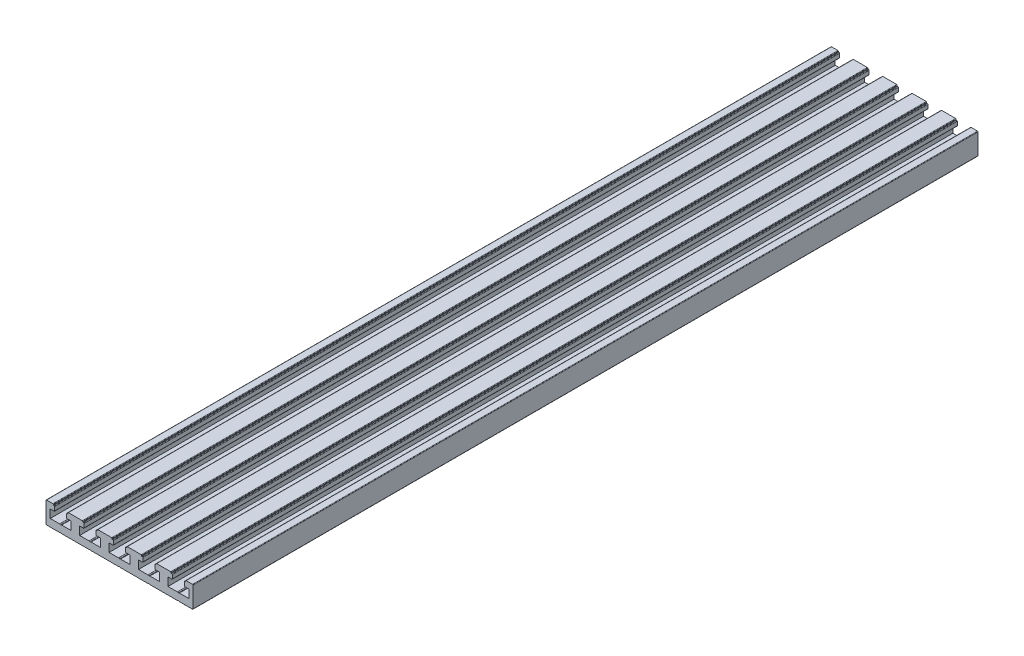
SolidWorks part; units mm, degrees
material "6061-T6 (SS)"
ref_plane "Front Plane" through (0, 0, 0) normal (0, 0, 1) x (1, 0, 0)
ref_plane "Top Plane" through (0, 0, 0) normal (0, 1, 0) x (1, 0, 0)
ref_plane "Right Plane" through (0, 0, 0) normal (1, 0, 0) x (0, 0, -1)
sketch "Sketch1" plane through (0, 0, 0) normal (0, 0, -1) x (-1, 0, 0)
  line L0 (0, 1.72) -> (0, -1.72) construction
  line L1 (-37.45, 8.85) -> (-37.45, -1.65)
  line L2 (-37.2, -1.9) -> (-30.5436, -1.9)
  line L3 (-30.4589, -1.8852) -> (-30, -1.72)
  line L4 (-30, -1.72) -> (-29.5411, -1.8852)
  line L5 (-29.4564, -1.9) -> (-15.5436, -1.9)
  line L6 (-15.4589, -1.8852) -> (-15, -1.72)
  line L7 (-15, -1.72) -> (-14.5411, -1.8852)
  line L8 (-14.4564, -1.9) -> (-0.5436, -1.9)
  line L9 (-0.4589, -1.8852) -> (0, -1.72)
  line L10 (0, -1.72) -> (0.4589, -1.8852)
  line L11 (0.5436, -1.9) -> (14.4564, -1.9)
  line L12 (14.5411, -1.8852) -> (15, -1.72)
  line L13 (15, -1.72) -> (15.4589, -1.8852)
  line L14 (15.5436, -1.9) -> (29.4564, -1.9)
  line L15 (29.5411, -1.8852) -> (30, -1.72)
  line L16 (30, -1.72) -> (30.4589, -1.8852)
  line L17 (30.5436, -1.9) -> (37.2, -1.9)
  line L18 (37.45, -1.65) -> (37.45, 8.85)
  line L19 (37.2, 9.1) -> (33.95, 9.1)
  line L20 (33.7, 8.85) -> (33.7, 8.5)
  line L21 (33.7, 8.5) -> (33.32, 8.5)
  line L22 (33.07, 8.25) -> (33.07, 6.35)
  line L23 (33.32, 6.1) -> (35.3, 6.1)
  line L24 (35.3, 6.1) -> (35.3, 1.9)
  line L25 (35.3, 1.9) -> (30.5436, 1.9)
  line L26 (30.4589, 1.8852) -> (30, 1.72)
  line L27 (30, 1.72) -> (29.5411, 1.8852)
  line L28 (29.4564, 1.9) -> (24.7, 1.9)
  line L29 (24.7, 1.9) -> (24.7, 6.1)
  line L30 (24.7, 6.1) -> (26.68, 6.1)
  line L31 (26.93, 6.35) -> (26.93, 8.25)
  line L32 (26.68, 8.5) -> (26.3, 8.5)
  line L33 (26.3, 8.5) -> (26.3, 8.85)
  line L34 (26.05, 9.1) -> (18.95, 9.1)
  line L35 (18.7, 8.85) -> (18.7, 8.5)
  line L36 (18.7, 8.5) -> (18.32, 8.5)
  line L37 (18.07, 8.25) -> (18.07, 6.35)
  line L38 (18.32, 6.1) -> (20.3, 6.1)
  line L39 (20.3, 6.1) -> (20.3, 1.9)
  line L40 (20.3, 1.9) -> (15.5436, 1.9)
  line L41 (15.4589, 1.8852) -> (15, 1.72)
  line L42 (15, 1.72) -> (14.5411, 1.8852)
  line L43 (14.4564, 1.9) -> (9.7, 1.9)
  line L44 (9.7, 1.9) -> (9.7, 6.1)
  line L45 (9.7, 6.1) -> (11.68, 6.1)
  line L46 (11.93, 6.35) -> (11.93, 8.25)
  line L47 (11.68, 8.5) -> (11.3, 8.5)
  line L48 (11.3, 8.5) -> (11.3, 8.85)
  line L49 (11.05, 9.1) -> (3.95, 9.1)
  line L50 (3.7, 8.85) -> (3.7, 8.5)
  line L51 (3.7, 8.5) -> (3.32, 8.5)
  line L52 (3.07, 8.25) -> (3.07, 6.35)
  line L53 (3.32, 6.1) -> (5.3, 6.1)
  line L54 (5.3, 6.1) -> (5.3, 1.9)
  line L55 (5.3, 1.9) -> (0.5436, 1.9)
  line L56 (0.4589, 1.8852) -> (0, 1.72)
  line L57 (0, 1.72) -> (-0.4589, 1.8852)
  line L58 (-0.5436, 1.9) -> (-5.3, 1.9)
  line L59 (-5.3, 1.9) -> (-5.3, 6.1)
  line L60 (-5.3, 6.1) -> (-3.32, 6.1)
  line L61 (-3.07, 6.35) -> (-3.07, 8.25)
  line L62 (-3.32, 8.5) -> (-3.7, 8.5)
  line L63 (-3.7, 8.5) -> (-3.7, 8.85)
  line L64 (-3.95, 9.1) -> (-11.05, 9.1)
  line L65 (-11.3, 8.85) -> (-11.3, 8.5)
  line L66 (-11.3, 8.5) -> (-11.68, 8.5)
  line L67 (-11.93, 8.25) -> (-11.93, 6.35)
  line L68 (-11.68, 6.1) -> (-9.7, 6.1)
  line L69 (-9.7, 6.1) -> (-9.7, 1.9)
  line L70 (-9.7, 1.9) -> (-14.4564, 1.9)
  line L71 (-14.5411, 1.8852) -> (-15, 1.72)
  line L72 (-15, 1.72) -> (-15.4589, 1.8852)
  line L73 (-15.5436, 1.9) -> (-20.3, 1.9)
  line L74 (-20.3, 1.9) -> (-20.3, 6.1)
  line L75 (-20.3, 6.1) -> (-18.32, 6.1)
  line L76 (-18.07, 6.35) -> (-18.07, 8.25)
  line L77 (-18.32, 8.5) -> (-18.7, 8.5)
  line L78 (-18.7, 8.5) -> (-18.7, 8.85)
  line L79 (-18.95, 9.1) -> (-26.05, 9.1)
  line L80 (-26.3, 8.85) -> (-26.3, 8.5)
  line L81 (-26.3, 8.5) -> (-26.68, 8.5)
  line L82 (-26.93, 8.25) -> (-26.93, 6.35)
  line L83 (-26.68, 6.1) -> (-24.7, 6.1)
  line L84 (-24.7, 6.1) -> (-24.7, 1.9)
  line L85 (-24.7, 1.9) -> (-29.4564, 1.9)
  line L86 (-29.5411, 1.8852) -> (-30, 1.72)
  line L87 (-30, 1.72) -> (-30.4589, 1.8852)
  line L88 (-30.5436, 1.9) -> (-35.3, 1.9)
  line L89 (-35.3, 1.9) -> (-35.3, 6.1)
  line L90 (-35.3, 6.1) -> (-33.32, 6.1)
  line L91 (-33.07, 6.35) -> (-33.07, 8.25)
  line L92 (-33.32, 8.5) -> (-33.7, 8.5)
  line L93 (-33.7, 8.5) -> (-33.7, 8.85)
  line L94 (-33.95, 9.1) -> (-37.2, 9.1)
  arc A0 (-37.45, -1.65) -> (-37.2, -1.9) centre (-37.2, -1.65) ccw
  arc A1 (-30.5436, -1.9) -> (-30.4589, -1.8852) centre (-30.5436, -1.65) ccw
  arc A2 (-29.5411, -1.8852) -> (-29.4564, -1.9) centre (-29.4564, -1.65) ccw
  arc A3 (-15.5436, -1.9) -> (-15.4589, -1.8852) centre (-15.5436, -1.65) ccw
  arc A4 (-14.5411, -1.8852) -> (-14.4564, -1.9) centre (-14.4564, -1.65) ccw
  arc A5 (-0.5436, -1.9) -> (-0.4589, -1.8852) centre (-0.5436, -1.65) ccw
  arc A6 (0.4589, -1.8852) -> (0.5436, -1.9) centre (0.5436, -1.65) ccw
  arc A7 (14.4564, -1.9) -> (14.5411, -1.8852) centre (14.4564, -1.65) ccw
  arc A8 (15.4589, -1.8852) -> (15.5436, -1.9) centre (15.5436, -1.65) ccw
  arc A9 (29.4564, -1.9) -> (29.5411, -1.8852) centre (29.4564, -1.65) ccw
  arc A10 (30.4589, -1.8852) -> (30.5436, -1.9) centre (30.5436, -1.65) ccw
  arc A11 (37.2, -1.9) -> (37.45, -1.65) centre (37.2, -1.65) ccw
  arc A12 (37.45, 8.85) -> (37.2, 9.1) centre (37.2, 8.85) ccw
  arc A13 (33.95, 9.1) -> (33.7, 8.85) centre (33.95, 8.85) ccw
  arc A14 (33.32, 8.5) -> (33.07, 8.25) centre (33.32, 8.25) ccw
  arc A15 (33.07, 6.35) -> (33.32, 6.1) centre (33.32, 6.35) ccw
  arc A16 (30.5436, 1.9) -> (30.4589, 1.8852) centre (30.5436, 1.65) ccw
  arc A17 (29.5411, 1.8852) -> (29.4564, 1.9) centre (29.4564, 1.65) ccw
  arc A18 (26.68, 6.1) -> (26.93, 6.35) centre (26.68, 6.35) ccw
  arc A19 (26.93, 8.25) -> (26.68, 8.5) centre (26.68, 8.25) ccw
  arc A20 (26.3, 8.85) -> (26.05, 9.1) centre (26.05, 8.85) ccw
  arc A21 (18.95, 9.1) -> (18.7, 8.85) centre (18.95, 8.85) ccw
  arc A22 (18.32, 8.5) -> (18.07, 8.25) centre (18.32, 8.25) ccw
  arc A23 (18.07, 6.35) -> (18.32, 6.1) centre (18.32, 6.35) ccw
  arc A24 (15.5436, 1.9) -> (15.4589, 1.8852) centre (15.5436, 1.65) ccw
  arc A25 (14.5411, 1.8852) -> (14.4564, 1.9) centre (14.4564, 1.65) ccw
  arc A26 (11.68, 6.1) -> (11.93, 6.35) centre (11.68, 6.35) ccw
  arc A27 (11.93, 8.25) -> (11.68, 8.5) centre (11.68, 8.25) ccw
  arc A28 (11.3, 8.85) -> (11.05, 9.1) centre (11.05, 8.85) ccw
  arc A29 (3.95, 9.1) -> (3.7, 8.85) centre (3.95, 8.85) ccw
  arc A30 (3.32, 8.5) -> (3.07, 8.25) centre (3.32, 8.25) ccw
  arc A31 (3.07, 6.35) -> (3.32, 6.1) centre (3.32, 6.35) ccw
  arc A32 (0.5436, 1.9) -> (0.4589, 1.8852) centre (0.5436, 1.65) ccw
  arc A33 (-0.4589, 1.8852) -> (-0.5436, 1.9) centre (-0.5436, 1.65) ccw
  arc A34 (-3.32, 6.1) -> (-3.07, 6.35) centre (-3.32, 6.35) ccw
  arc A35 (-3.07, 8.25) -> (-3.32, 8.5) centre (-3.32, 8.25) ccw
  arc A36 (-3.7, 8.85) -> (-3.95, 9.1) centre (-3.95, 8.85) ccw
  arc A37 (-11.05, 9.1) -> (-11.3, 8.85) centre (-11.05, 8.85) ccw
  arc A38 (-11.68, 8.5) -> (-11.93, 8.25) centre (-11.68, 8.25) ccw
  arc A39 (-11.93, 6.35) -> (-11.68, 6.1) centre (-11.68, 6.35) ccw
  arc A40 (-14.4564, 1.9) -> (-14.5411, 1.8852) centre (-14.4564, 1.65) ccw
  arc A41 (-15.4589, 1.8852) -> (-15.5436, 1.9) centre (-15.5436, 1.65) ccw
  arc A42 (-18.32, 6.1) -> (-18.07, 6.35) centre (-18.32, 6.35) ccw
  arc A43 (-18.07, 8.25) -> (-18.32, 8.5) centre (-18.32, 8.25) ccw
  arc A44 (-18.7, 8.85) -> (-18.95, 9.1) centre (-18.95, 8.85) ccw
  arc A45 (-26.05, 9.1) -> (-26.3, 8.85) centre (-26.05, 8.85) ccw
  arc A46 (-26.68, 8.5) -> (-26.93, 8.25) centre (-26.68, 8.25) ccw
  arc A47 (-26.93, 6.35) -> (-26.68, 6.1) centre (-26.68, 6.35) ccw
  arc A48 (-29.4564, 1.9) -> (-29.5411, 1.8852) centre (-29.4564, 1.65) ccw
  arc A49 (-30.4589, 1.8852) -> (-30.5436, 1.9) centre (-30.5436, 1.65) ccw
  arc A50 (-33.32, 6.1) -> (-33.07, 6.35) centre (-33.32, 6.35) ccw
  arc A51 (-33.07, 8.25) -> (-33.32, 8.5) centre (-33.32, 8.25) ccw
  arc A52 (-33.7, 8.85) -> (-33.95, 9.1) centre (-33.95, 8.85) ccw
  arc A53 (-37.2, 9.1) -> (-37.45, 8.85) centre (-37.2, 8.85) ccw
  point P2 (0, 0)
  dimension "D1" = 11
  dimension "D2" = 74.9
extrude "RawPart" add sketch "Sketch1" against normal blind 400
hole_wizard "CSK for M3 Flat Head Machine Screw1" positions "3DSketch1" profile "Sketch2" countersink size "M3" standard "ANSI Metric" end condition through all
sketch3d "3DSketch1"
  point P0 (-30, 1.9, 65)
  point P2 (30, 1.9, 65)
  point P35 (30, 1.9, 330)
  point P37 (-30, 1.9, 330)
  dimension "D4" = 330
  dimension "D1" = 65
  dimension "D2" = 7.45
  dimension "D3" = 60
sketch "Sketch2" plane through (-30, 1.9, 65) normal (1, 0, 0) x (0, 0, 1)
  line L0 (0, 0) -> (0, 3.8)
  line L1 (0, 3.8) -> (1.6, 3.8)
  line L2 (1.6, 3.8) -> (1.6, 1.9)
  line L3 (1.6, 1.9) -> (3, 0.5)
  line L4 (3, 0.5) -> (3, 0)
  line L6 (3, 0) -> (0, 0)
  line L7 (-1.6, 1.9) -> (-3, 0.5) construction
  line L11 (0, -6.35) -> (0, 107.95) construction
  dimension "Thru Hole Dia." = 3.2
  dimension "Thru Hole Depth" = 3.8
  dimension "C'Sink Dia." = 6
  dimension "C'Sink Angle" = 90
  dimension "Head Clearance" = 0.5
hole_wizard "M4x0.7 Tapped Hole1" positions "Sketch4" profile "Sketch5" tap size "M4x0.7" standard "ANSI Metric" end condition through all
sketch "Sketch4" plane through (0, 1.9, 0) normal (0, 1, 0) x (1, 0, 0)
  line L1 (-0.5436, 0) -> (-14.4564, 0) construction
  line L2 (-37.45, -400) -> (-37.45, 0) construction
  line L3 (15, -400) -> (15, 0) construction
  line L5 (-26.05, 0) -> (-18.95, 0) construction
  point P0 (15, -30)
  point P15 (15, -372)
  dimension "D1" = 30
  dimension "D2" = 52.45
  dimension "D3" = 372
sketch "Sketch5" plane through (15, 1.9, 30) normal (1, 0, 0) x (0, 0, 1)
  line L0 (0, 0) -> (0, 3.8)
  line L1 (0, 3.8) -> (1.65, 3.8)
  line L2 (1.65, 3.8) -> (1.65, 0)
  line L5 (1.65, 0) -> (0, 0)
  line L11 (0, -6.35) -> (0, 107.95) construction
  dimension "Thru Tap Drill Dia." = 3.3
  dimension "Thru Tap Drill Depth" = 3.8
cosmetic thread "Hole Thread4" parameters "D2"=4
cosmetic thread "Hole Thread8" parameters "D2"=4
sketch "Sketch6" [suppressed] plane through (0, 0, 0) normal (0, 0, -1) x (-1, 0, 0)
  line L1 (-14.5411, -9.9057) -> (-41.3903, -9.9057)
  line L2 (-14.5411, -9.9057) -> (-14.5411, 14.5956)
  line L3 (-14.5411, 14.5956) -> (-41.3903, 14.5956)
  line L4 (-41.3903, -9.9057) -> (-41.3903, 14.5956)
extrude "CutUnnecessaryHalf" [suppressed] cut sketch "Sketch6" against normal through all
equation "\"D4@3DSketch1\" = \"D1@RawPart\" - \"D1@3DSketch1\" - 5"
